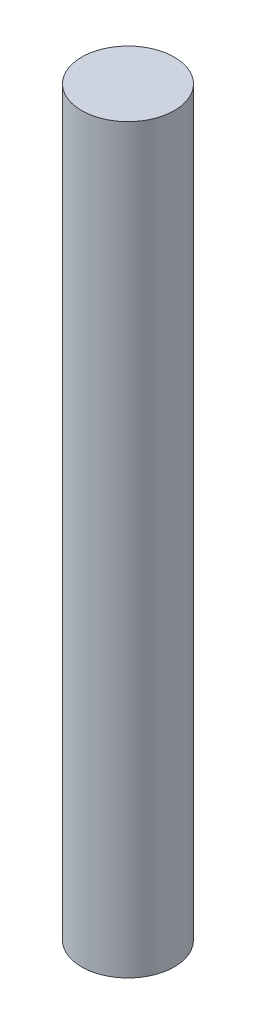
SolidWorks part; units mm, degrees
ref_plane "Front Plane" through (0, 0, 0) normal (0, 0, 1) x (1, 0, 0)
ref_plane "Top Plane" through (0, 0, 0) normal (0, 1, 0) x (1, 0, 0)
ref_plane "Right Plane" through (0, 0, 0) normal (1, 0, 0) x (0, 0, -1)
sketch "Sketch1" plane through (0, 0, 0) normal (0, 1, 0) x (1, 0, 0)
  circle A0 centre (0, 0) radius 9.525
  dimension "D1" = 19.05
extrude "Boss-Extrude1" add sketch "Sketch1" against normal blind 152.4
